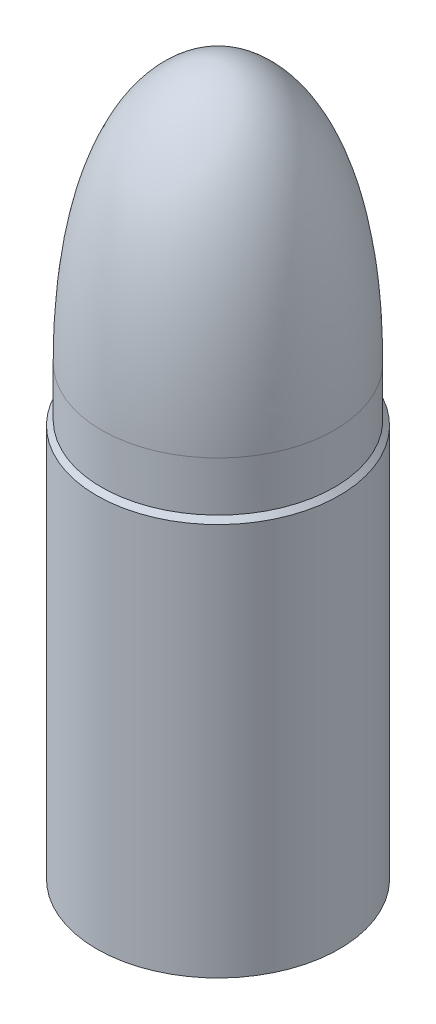
SolidWorks part; units mm, degrees
ref_plane "Front Plane" through (0, 0, 0) normal (0, 0, 1) x (1, 0, 0)
ref_plane "Top Plane" through (0, 0, 0) normal (0, 1, 0) x (1, 0, 0)
ref_plane "Right Plane" through (0, 0, 0) normal (1, 0, 0) x (0, 0, -1)
sketch "Sketch1" plane through (0, 0, 0) normal (0, 1, 0) x (1, 0, 0)
  circle A0 centre (0, 0) radius 35
  circle A1 centre (0, 0) radius 36.5
  dimension "D1" = 70
  dimension "D2" = 1.5
extrude "Boss-Extrude1" add sketch "Sketch1" along normal blind 20
sketch "Sketch2" plane through (0, 0, 0) normal (0, 0, 1) x (1, 0, 0)
  line L0 (0, 20) -> (0, 204.6854) construction
  line L1 (36.5, 20) -> (-36.5, 20) construction
  line L2 (-35, 158.3922) -> (-35, 91.6078) construction
  line L3 (26.0425, 100) -> (-26.0425, 100) construction
  line L4 (-35, 20) -> (-36.5, 20)
  line L5 (0, 100) -> (0, 101.5)
  spline S0 degree 3 poles (-35, 20) (-35, 80.3323) (-14.3763, 100) (0, 100) knots 0 0 0 0 1 1 1 1
  spline S1 degree 1 poles (-36.5, 20) (0, 101.5) knots 0 0 1 1 construction
  spline S2 degree 3 poles (-36.5, 20) (-36.5, 20.9382) (-36.4899, 22.8288) (-36.4299, 26.4961) (-36.282, 30.9469) (-35.9927, 36.0536) (-35.4641, 42.5641) (-34.5476, 50.1485) (-33.0768, 58.3966) (-31.2726, 65.8221) (-28.4724, 74.6676) (-24.325, 83.8228) (-18.6037, 92.0058) (-13.4542, 96.6741) (-9.2547, 99.2168) (-6.1042, 100.55) (-3.5167, 101.2014) (-1.4847, 101.4579) (-0.4978, 101.5) (0, 101.5) knots 0 0 0 0 0.015625 0.03125 0.0625 0.09375 0.125 0.1875 0.25 0.3125 0.375 0.5 0.625 0.75 0.8125 0.875 0.9375 0.96875 1 1 1 1
  dimension "D1" = 80
revolve "Revolve1" add sketch "Sketch2" angle 360 about L0
sketch "Sketch3" plane through (0, 0, 0) normal (0, -1, 0) x (1, 0, 0)
  circle A0 centre (0, 0) radius 36.5 construction
  circle A1 centre (0, 0) radius 36.5
  circle A2 centre (0, 0) radius 38
  dimension "D1" = 1.5
extrude "Boss-Extrude2" add sketch "Sketch3" along normal blind 120 and the other way blind 5
chamfer "Chamfer1" distance 2 angle 45 1 edges at (0, 5, -38)
sketch "Sketch4" plane through (0, -120, 0) normal (0, -1, 0) x (1, 0, 0)
  circle A0 centre (0, 0) radius 37.15
  dimension "D1" = 74.3
extrude "Cut-Extrude1" cut sketch "Sketch4" against normal up to surface (120 mm away) up to face at (0, 0, 36.5)
